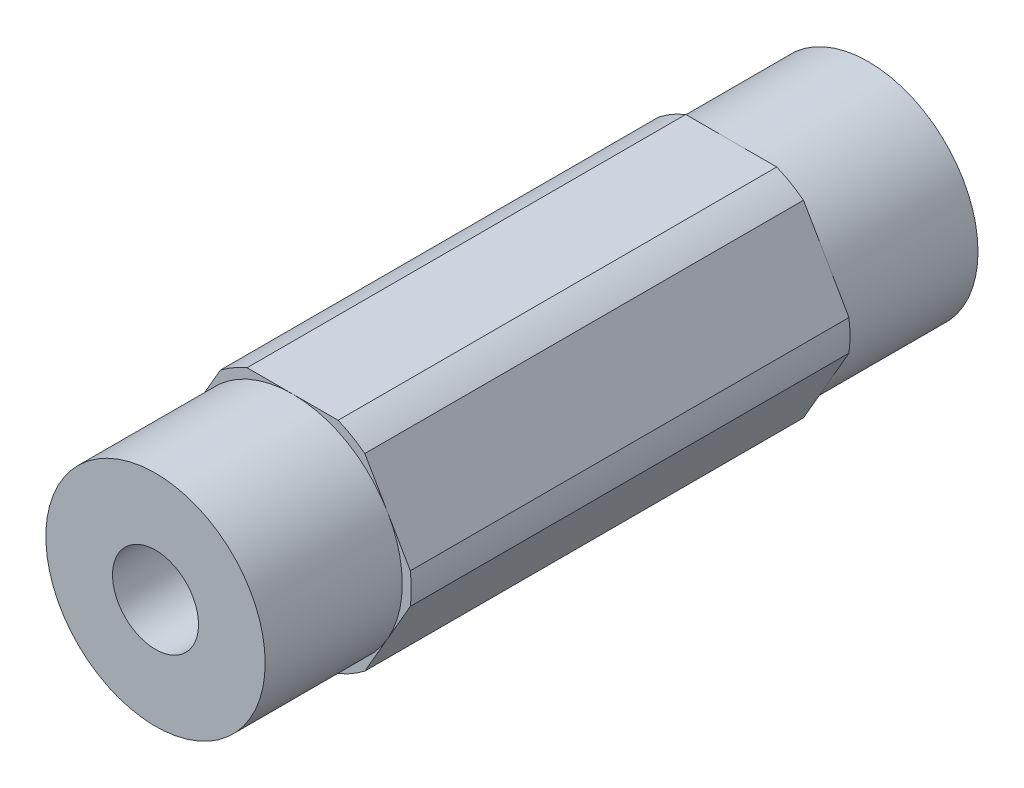
SolidWorks part; units mm, degrees
material "6061-T6 (SS)"
ref_plane "Front Plane" through (0, 0, 0) normal (0, 0, 1) x (1, 0, 0)
ref_plane "Top Plane" through (0, 0, 0) normal (0, 1, 0) x (1, 0, 0)
ref_plane "Right Plane" through (0, 0, 0) normal (1, 0, 0) x (0, 0, -1)
sketch "Sketch1" plane through (0, 0, 0) normal (0, 0, 1) x (1, 0, 0)
  line L1 (3.6662, 6.35) -> (-3.6662, 6.35)
  line L2 (-3.6662, 6.35) -> (-7.3323, 0)
  line L3 (-7.3323, 0) -> (-3.6662, -6.35)
  line L4 (-3.6662, -6.35) -> (3.6662, -6.35)
  line L5 (3.6662, -6.35) -> (7.3323, 0)
  line L6 (7.3323, 0) -> (3.6662, 6.35)
  circle A0 centre (0, 0) radius 6.35 construction
  circle A1 centre (0, 0) radius 2.4892
  circle A2 centre (0, 0) radius 6.875
  point P1 (0, 6.35)
  dimension "D1" = 12.7
  dimension "D2" = 4.9784
  dimension "D3" = 13.75
extrude "Boss-Extrude1" add sketch "Sketch1" along normal mid plane 41.275 contours L6 A2 L1 L2 L3 L4 L5 A1 region at (3.3439, 5.7918, 0)
sketch "Sketch2" plane through (0, 0, 20.6375) normal (0, 0, 1) x (1, 0, 0)
  circle A0 centre (0, 0) radius 6.35
  dimension "D1" = 12.7
extrude "Cut-Extrude4" cut sketch "Sketch2" against normal blind 7.9375 flip side to cut contours A0 region at (0, 0, 20.6375)
mirror "Mirror1" about plane through (0, 0, 0) normal (0, 0, 1) of "Cut-Extrude4"
equation "\"D3@Sketch1\"=13.75mm"
